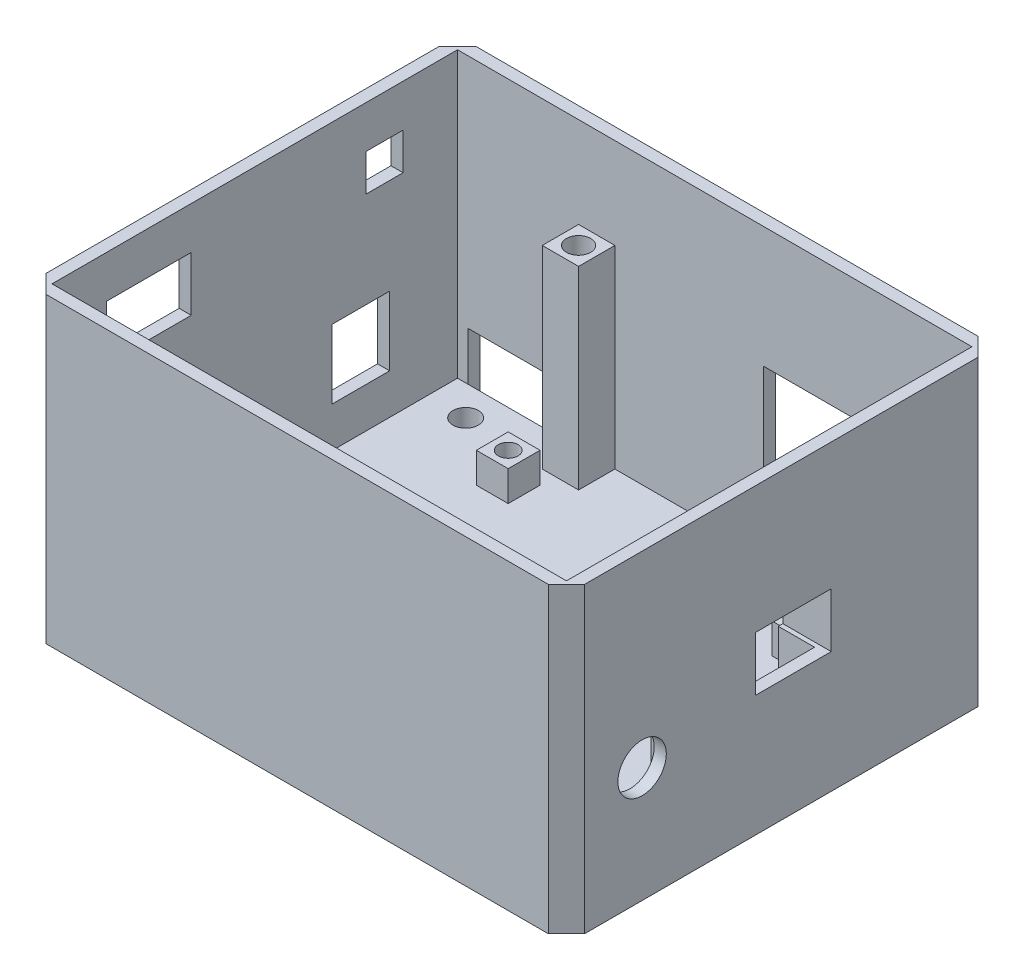
SolidWorks part; units mm, degrees
ref_plane "Front Plane" through (0, 0, 0) normal (0, 0, 1) x (1, 0, 0)
ref_plane "Top Plane" through (0, 0, 0) normal (0, 1, 0) x (1, 0, 0)
ref_plane "Right Plane" through (0, 0, 0) normal (1, 0, 0) x (0, 0, -1)
sketch "Sketch1" plane through (0, 0, 0) normal (0, 1, 0) x (1, 0, 0)
  line L0 (-44.5, 35.5) -> (44.5, 35.5)
  line L1 (-42.5, -33.5) -> (42.5, -33.5)
  line L2 (-42.5, -33.5) -> (-42.5, 33.5)
  line L3 (-42.5, 33.5) -> (42.5, 33.5)
  line L4 (42.5, -33.5) -> (42.5, 33.5)
  line L5 (-42.5, -33.5) -> (42.5, 33.5) construction
  line L6 (-42.5, 33.5) -> (42.5, -33.5) construction
  line L7 (44.5, -35.5) -> (44.5, 35.5)
  line L8 (-44.5, -35.5) -> (44.5, -35.5)
  line L9 (-44.5, -35.5) -> (-44.5, 35.5)
  circle A0 centre (-36.1567, 28.5) radius 2.1
  circle A1 centre (36.1567, 28.5) radius 2.1
  circle A3 centre (36.1567, -28.5) radius 2.1
  point P0 (0, 0)
  dimension "D4" = 4.2
  dimension "D1" = 85
  dimension "D2" = 67
  dimension "D5" = 5
  dimension "D3" = 2
extrude "Boss-Extrude1" add sketch "Sketch1" along normal blind 3 contours L1 L4 L3 L2 A3 A1 A0 region at (-0.0886, 0, 0.0698)
extrude "Boss-Extrude2" add sketch "Sketch1<3>" along normal blind 50 contours L9 L8 L7 L0 L4 L1 L2 L3 region at (0, 0, -34.3615)
sketch "Sketch1<3>" plane through (0, 0, 0) normal (0, 1, 0) x (1, 0, 0) same geometry as "Sketch1"
chamfer "Chamfer1" distance 3 angle 45 4 edges at (-44.5, 25, 35.5) (-44.5, 25, -35.5) (44.5, 25, -35.5) (44.5, 25, 35.5)
sketch "Sketch2" plane through (0, 3, 0) normal (0, 1, 0) x (1, 0, 0)
  line L0 (-42.5, 33.5) -> (42.5, 33.5) construction
  line L1 (-22.5, 33.5) -> (-16.5, 33.5)
  line L2 (-22.5, 33.5) -> (-22.5, 27.5)
  line L3 (-22.5, 27.5) -> (-16.5, 27.5)
  line L4 (-16.5, 33.5) -> (-16.5, 27.5)
  line L5 (42.5, -33.5) -> (42.5, 33.5) construction
  line L6 (42.5, 13.5) -> (36.5, 13.5)
  line L7 (42.5, 13.5) -> (42.5, 7.5)
  line L8 (42.5, 7.5) -> (36.5, 7.5)
  line L9 (36.5, 13.5) -> (36.5, 7.5)
  line L10 (42.5, -33.5) -> (42.5, 33.5) construction
  line L11 (42.5, -7.5) -> (36.5, -7.5)
  line L12 (42.5, -7.5) -> (42.5, -13.5)
  line L13 (42.5, -13.5) -> (36.5, -13.5)
  line L14 (36.5, -7.5) -> (36.5, -13.5)
  line L15 (-16.5, 33.5) -> (-22.5, 27.5) construction
  line L16 (36.5, 13.5) -> (42.5, 7.5) construction
  line L17 (36.5, -7.5) -> (42.5, -13.5) construction
  line L19 (-42.5, -33.5) -> (-42.5, 33.5) construction
  line L20 (-42.5, 33.5) -> (42.5, 33.5) construction
  line L21 (-42.5, -33.5) -> (42.5, -33.5) construction
  circle A0 centre (-19.5, 30.5) radius 2
  circle A1 centre (39.5, 10.5) radius 2
  circle A2 centre (39.5, -10.5) radius 2
  dimension "D5" = 4
  dimension "D1" = 6
  dimension "D2" = 20
  dimension "D3" = 20
  dimension "D4" = 26
extrude "Boss-Extrude3" add sketch "Sketch2" along normal offset from surface (32 mm away) 15 up to face at (0, 50, 0)
sketch "Sketch4" plane through (0, 3, 0) normal (0, 1, 0) x (1, 0, 0)
  line L0 (-156.8658, 19.0233) -> (-98.3658, 19.0233)
  line L1 (-98.3658, 19.0233) -> (-98.3658, -52.7267)
  line L2 (-98.3658, -52.7267) -> (-156.8658, -52.7267)
  line L3 (-156.8658, -52.7267) -> (-156.8658, 19.0233)
  line L4 (-42.5, -33.5) -> (-42.5, 25)
  line L5 (-42.5, 25) -> (29.25, 25)
  line L6 (29.25, 25) -> (29.25, -33.5)
  line L7 (29.25, -33.5) -> (-42.5, -33.5)
  line L9 (-25.63, 19.74) -> (-20.37, 19.74)
  line L10 (-25.63, 19.74) -> (-25.63, 25)
  line L11 (-25.63, 25) -> (-20.37, 25)
  line L12 (-20.37, 19.74) -> (-20.37, 25)
  line L13 (-25.63, 19.74) -> (-20.37, 25) construction
  line L14 (-25.63, 25) -> (-20.37, 19.74) construction
  line L15 (23.19, 19.74) -> (29.25, 19.74)
  line L16 (23.19, 19.74) -> (23.19, 25)
  line L17 (23.19, 25) -> (29.25, 25)
  line L18 (29.25, 19.74) -> (29.25, 25)
  line L19 (23.19, 19.74) -> (29.25, 25) construction
  line L20 (23.19, 25) -> (29.25, 19.74) construction
  line L21 (23.19, -28.24) -> (29.25, -28.24)
  line L22 (23.19, -28.24) -> (23.19, -33.5)
  line L23 (23.19, -33.5) -> (29.25, -33.5)
  line L24 (29.25, -28.24) -> (29.25, -33.5)
  line L25 (23.19, -28.24) -> (29.25, -33.5) construction
  line L26 (23.19, -33.5) -> (29.25, -28.24) construction
  line L27 (-36.44, -28.24) -> (-42.5, -28.24)
  line L28 (-36.44, -28.24) -> (-36.44, -33.5)
  line L29 (-36.44, -33.5) -> (-42.5, -33.5)
  line L30 (-42.5, -28.24) -> (-42.5, -33.5)
  line L31 (-36.44, -28.24) -> (-42.5, -33.5) construction
  line L32 (-36.44, -33.5) -> (-42.5, -28.24) construction
  circle A0 centre (-154.2408, 15.9983) radius 1.625
  circle A1 centre (-100.9908, -0.4517) radius 1.625
  circle A2 centre (-153.9908, -49.7017) radius 1.625
  circle A3 centre (-100.9908, -49.6017) radius 1.625
  circle A4 centre (-39.47, -30.87) radius 1.625
  circle A5 centre (26.22, -30.87) radius 1.625
  circle A6 centre (26.22, 22.37) radius 1.625
  circle A7 centre (-23, 22.37) radius 1.625
  line M23 (-42.5, -33.5) -> (42.5, -33.5)
  dimension "D3" = 3.25
  dimension "D14" = 3.25
  dimension "D1" = 58.5
  dimension "D2" = 71.75
  dimension "D4" = 2.625
  dimension "D5" = 3.025
  dimension "D6" = 2.625
  dimension "D7" = 19.475
  dimension "D8" = 2.625
  dimension "D9" = 3.125
  dimension "D10" = 2.875
  dimension "D11" = 3.025
  dimension "D12" = 71.75
  dimension "D13" = 58.5
  dimension "D15" = 2.63
  dimension "D16" = 3.03
  dimension "D17" = 3.03
  dimension "D18" = 2.63
  dimension "D19" = 19.5
extrude "Boss-Extrude4" add sketch "Sketch4" along normal blind 5 contours L28 L27 L4 A4 M23 | L9 L12 L5 L10 A7 | L16 L15 L6 L5 A6 | L21 L22 L7 L6 A5 region at (-42.4198, 3, 30.87) region at (23.2702, 3, 30.87) region at (-23, 3, -24.9256) region at (26.22, 3, -24.9198)
sketch "Sketch5" plane through (0, 0, -33.5) normal (0, 0, 1) x (1, 0, 0)
  line L1 (8.0442, 30) -> (23.0442, 30)
  line L2 (8.0442, 30) -> (8.0442, 10)
  line L3 (8.0442, 10) -> (23.0442, 10)
  line L4 (23.0442, 30) -> (23.0442, 10)
  line L5 (-40.7758, 11) -> (-23.7758, 11)
  line L6 (-40.7758, 11) -> (-40.7758, 0)
  line L7 (-40.7758, 0) -> (-23.7758, 0)
  line L8 (-23.7758, 11) -> (-23.7758, 0)
extrude "Cut-Extrude1" cut sketch "Sketch5" against normal blind 3
sketch "Sketch6" plane through (-42.5, 0, 0) normal (1, 0, 0) x (0, 0, -1)
  line L0 (22.2843, 21.0681) -> (12.7412, 21.0681)
  line L1 (12.7412, 21.0681) -> (12.7412, 9.6621)
  line L2 (12.7412, 9.6621) -> (22.2843, 9.6621)
  line L3 (22.2843, 9.6621) -> (22.2843, 21.0681)
  line L4 (-32.5, 50) -> (32.5, 50) construction
  line L5 (-10.5, 43) -> (-24.5, 43)
  line L6 (-10.5, 43) -> (-10.5, 34)
  line L7 (-10.5, 34) -> (-24.5, 34)
  line L8 (-24.5, 43) -> (-24.5, 34)
  line L10 (33.5, 50) -> (33.5, 3) construction
  line L11 (18.4, 36.9) -> (24.5, 36.9)
  line L12 (18.4, 36.9) -> (18.4, 43)
  line L13 (18.4, 43) -> (24.5, 43)
  line L14 (24.5, 36.9) -> (24.5, 43)
  line L15 (18.4, 36.9) -> (24.5, 43) construction
  line L16 (18.4, 43) -> (24.5, 36.9) construction
  line L17 (-33.5, 50) -> (-33.5, 8) construction
  point P12 (21.45, 39.95)
  dimension "D1" = 14
  dimension "D2" = 9
  dimension "D3" = 7
  dimension "D4" = 9
  dimension "D5" = 6.1
  dimension "D6" = 9
sketch "Sketch7" plane through (44.5, 0, 0) normal (1, 0, 0) x (0, 0, -1)
  line L0 (-32.5, 50) -> (-32.5, 0) construction
  line L1 (-4.25, 29) -> (8.25, 29)
  line L2 (-4.25, 29) -> (-4.25, 20)
  line L3 (-4.25, 20) -> (8.25, 20)
  line L4 (8.25, 29) -> (8.25, 20)
  line L5 (-4.25, 29) -> (8.25, 20) construction
  line L6 (-4.25, 20) -> (8.25, 29) construction
  line L8 (-33.5, 50) -> (-33.5, 3) construction
  line L10 (-32.5, 0) -> (32.5, 0) construction
  circle A0 centre (-23, 19) radius 4
  circle A1 centre (-23, 19) radius 10.5 construction
  point P0 (2, 24.5)
  point P5 (0, 0)
  dimension "D1" = 8
  dimension "D2" = 21
  dimension "D3" = 24.5
  dimension "D4" = 9
  dimension "D5" = 12.5
  dimension "D6" = 19
  dimension "D7" = 34.5
extrude "Cut-Extrude2" cut sketch "Sketch7" against normal blind 10
extrude "Cut-Extrude3" cut sketch "Sketch6" against normal blind 10 contours L0 L1 L2 L3 | L6 L5 L8 L7 | L12 L11 L14 L13
